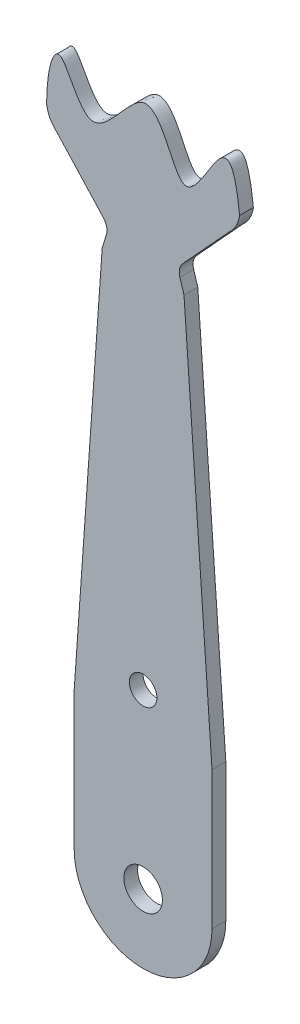
SolidWorks part; units mm, degrees
ref_plane "Alzado" through (0, 0, 0) normal (0, 0, 1) x (1, 0, 0)
ref_plane "Planta" through (0, 0, 0) normal (0, 1, 0) x (1, 0, 0)
ref_plane "Vista lateral" through (0, 0, 0) normal (1, 0, 0) x (0, 0, -1)
sketch "Model" plane through (0, 0, 0) normal (0, 0, 1) x (1, 0, 0)
  line L0 (48.0756, 24.9601) -> (51.4403, 28.631)
  line L1 (42.3364, 24.9601) -> (38.9717, 28.631)
  line L2 (42.5389, 24.0031) -> (42.2409, 23.0482)
  line L3 (42.2409, 23.0482) -> (40.206, -5.7616)
  line L4 (40.206, -5.7616) -> (40.206, -15.7616)
  line L5 (50.206, -15.7616) -> (50.206, -5.7616)
  line L6 (50.206, -5.7616) -> (48.1711, 23.0482)
  line L7 (48.1711, 23.0482) -> (47.8731, 24.0031)
  circle A0 centre (45.206, -3.2616) radius 1
  circle A1 centre (45.206, -15.7616) radius 1.4
  arc A2 (38.206, 30.0497) -> (38.9717, 28.631) centre (40.4747, 30.3582) ccw
  arc A3 (51.4403, 28.631) -> (52.206, 30.0497) centre (49.9373, 30.3582) ccw
  arc A4 (42.5389, 24.0031) -> (42.3364, 24.9601) centre (41.5843, 24.301) ccw
  arc A5 (40.206, -15.7616) -> (50.206, -15.7616) centre (45.206, -15.7616) ccw
  arc A6 (48.0756, 24.9601) -> (47.8731, 24.0031) centre (48.8276, 24.301) ccw
  spline S0 degree 3 poles (52.206, 30.0497) (51.4109, 37.4505) (48.5489, 24.4278) (45.9531, 36.7451) (41.2979, 28.0048) (39.0799, 35.7221) (38.203, 32.1045) (38.206, 30.0497) knots 0 0 0 0 0.352723 0.547894 0.704625 0.854468 1 1 1 1
base flange "Brida base1" sketch "Model" thickness 1 reverse thickness direction no parameters "D1"=0.7366
sketch "Líneas de pliegue1" [suppressed] plane through (0, 0, 0) normal (0, 1, 0) x (1, 0, 0)
sketch "Cuadro delimitador1" [suppressed] plane through (0, 0, 0) normal (0, 1, 0) x (1, 0, 0)
sheet metal parameters "Chapa metálica1" thickness 1 parameters "D1"=0.7366
flat pattern "Chapa desplegada1" [suppressed]
sketch "Líneas de pliegue2" plane through (0, 0, 0) normal (0, 1, 0) x (1, 0, 0)
sketch3d "Cuadro delimitador2" [suppressed]
  line L0 (-3.9015, -54.2987, 0) -> (-6.2681, 0.0396, 0) construction
  line L1 (10.0866, -53.6895, 0) -> (7.7199, 0.6489, 0) construction
  line L2 (-3.9015, -54.2987, 0) -> (10.0866, -53.6895, 0) construction
  line L3 (-6.2681, 0.0396, 0) -> (7.7199, 0.6489, 0) construction
